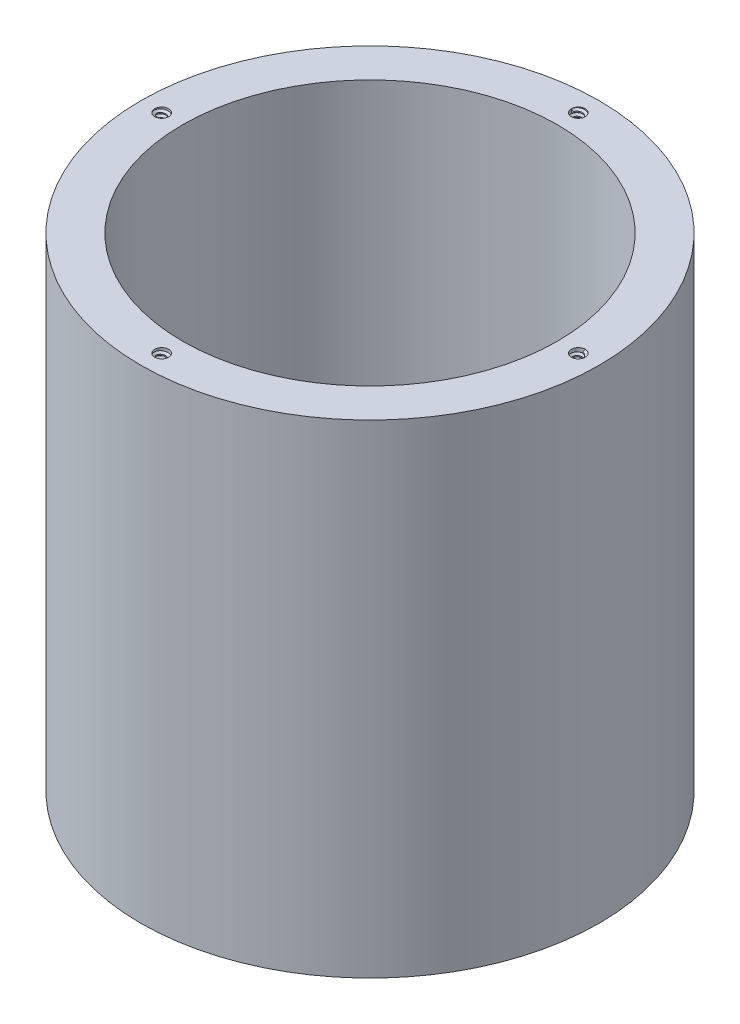
SolidWorks part; units mm, degrees
material "1060 Alloy"
ref_plane "Front Plane" through (0, 0, 0) normal (0, 0, 1) x (1, 0, 0)
ref_plane "Top Plane" through (0, 0, 0) normal (0, 1, 0) x (1, 0, 0)
ref_plane "Right Plane" through (0, 0, 0) normal (1, 0, 0) x (0, 0, -1)
sketch "Sketch1" plane through (0, 0, 0) normal (0, 1, 0) x (1, 0, 0)
  circle A0 centre (0, 0) radius 16.5
  circle A1 centre (0, 0) radius 13.5
  dimension "D1" = 33
  dimension "D2" = 27
extrude "Boss-Extrude1" add sketch "Sketch1" along normal blind 34.8
sketch "Sketch2" plane through (0, 34.8, 0) normal (0, 1, 0) x (1, 0, 0)
  circle A0 centre (0, 15) radius 0.5
  circle A2 centre (0, 0) radius 13.5 construction
  dimension "D1" = 1
  dimension "D2" = 15
extrude "Cut-Extrude1" cut sketch "Sketch2" against normal blind 2
thread "Thread1" pitch 0.3175 method extrude profile "Thread Profile1" start angle 0, offset 0, length 3.5, pitch 0.3175, diameter 1
ref_plane "Plane1" through (-0.5, 34.8, -15) normal (0, 0, 1) x (-1, 0, 0)
sketch "Thread Profile1" plane through (-0.5, 34.8, -15) normal (0, 0, 1) x (-1, 0, 0)
  line L0 (0, 0) -> (0, 0.3175) construction
  line L11 (0, 0) -> (0, 0.2778)
  line L12 (0, 0.2778) -> (-0.1719, 0.1786)
  line L13 (-0.1719, 0.1786) -> (-0.1719, 0.0992)
  line L15 (-0.1719, 0.0992) -> (0, 0)
  line L17 (-0.1719, 0.1389) -> (0, 0.1389) construction
  point P2 (0, 0)
  dimension "Pitch" = 0.3175
  dimension "Profile_Angle" = 60
  dimension "Profile_Land" = 0.0794
  dimension "Profile_Height" = 0.1719
pattern_circular "CirPattern1" count 4 over 360 about axis through (0, 34.8, 0) along (0, 1, 0) of "Cut-Extrude1", "Thread1"
sketch "Sketch5" plane through (0, 0, 0) normal (0, -1, 0) x (1, 0, 0)
  circle A0 centre (0, 15) radius 0.5
  dimension "D1" = 1
  dimension "D2" = 15
extrude "Cut-Extrude2" cut sketch "Sketch5" against normal blind 2
thread "Thread2" pitch 0.3175 method extrude profile "Thread Profile2" start angle 0, offset 0, length 3.5, pitch 0.3175, diameter 1
ref_plane "Plane2" through (0.5, 0, 15) normal (0, 0, 1) x (1, 0, 0)
sketch "Thread Profile2" plane through (0.5, 0, 15) normal (0, 0, 1) x (1, 0, 0)
  line L0 (0, 0) -> (0, 0.3175) construction
  line L11 (0, 0) -> (0, 0.2778)
  line L12 (0, 0.2778) -> (-0.1719, 0.1786)
  line L13 (-0.1719, 0.1786) -> (-0.1719, 0.0992)
  line L15 (-0.1719, 0.0992) -> (0, 0)
  line L17 (-0.1719, 0.1389) -> (0, 0.1389) construction
  point P2 (0, 0)
  dimension "Pitch" = 0.3175
  dimension "Profile_Angle" = 60
  dimension "Profile_Land" = 0.0794
  dimension "Profile_Height" = 0.1719
pattern_circular "CirPattern2" count 4 over 360 about axis through (0, 0, 0) along (0, 1, 0) of "Cut-Extrude2", "Thread2"
